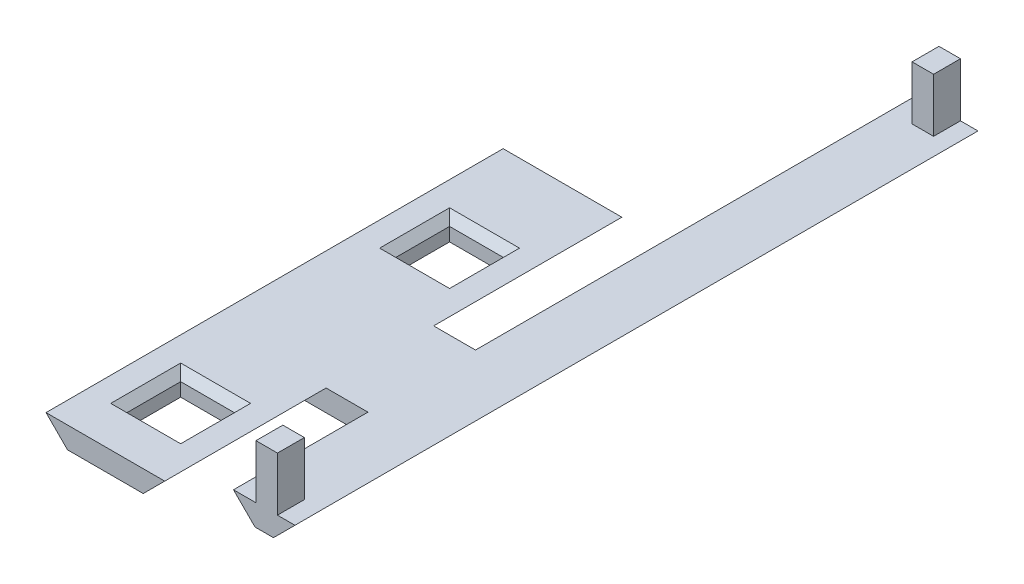
SolidWorks part; units mm, degrees
note: The reader was unsure of these and kept them because the rebuilt part matched: shared geometry of "Szkic1<4>".
ref_plane "Płaszczyzna przednia" through (0, 0, 0) normal (0, 0, 1) x (1, 0, 0)
ref_plane "Płaszczyzna górna" through (0, 0, 0) normal (0, 1, 0) x (1, 0, 0)
ref_plane "Płaszczyzna prawa" through (0, 0, 0) normal (1, 0, 0) x (0, 0, -1)
sketch "Szkic1" plane through (0, 0, 0) normal (0, 0, 1) x (1, 0, 0)
  line L0 (7.5, 0) -> (-7.5, 0)
  line L1 (-7.5, 0) -> (-11.5, 4)
  line L2 (-11.5, 4) -> (11.5, 4)
  line L3 (0, 0) -> (0, 34.0436) construction
  line L4 (7.5, 0) -> (11.5, 4)
  line L5 (-10.5787, 4) -> (-6.5787, 0)
  line L6 (10.5787, 4) -> (6.5787, 0)
  line L7 (23, 0) -> (27, 0)
  line L8 (19, 4) -> (31, 4)
  line L9 (31, 4) -> (27, 0)
  line L10 (23, 0) -> (19, 4)
  line L11 (25, 4) -> (25, 0) construction
  line L12 (19.2828, 4) -> (23.2828, 0)
  line L13 (30.7172, 4) -> (26.7172, 0)
  point P7 (0, 4)
  dimension "D1" = 45
  dimension "D2" = 15
  dimension "D3" = 4
  dimension "D4" = 0.6515
  dimension "D5" = 45
  dimension "D6" = 45
  dimension "D7" = 4
  dimension "D8" = 25
  dimension "D9" = 0.2
extrude "Dodanie-wyciągnięcie1" add sketch "Szkic1" along normal blind 85 contours L0 L3 L2 L5 | L3 L0 L6 L2
sketch "Szkic2" plane through (0, 0, 0) normal (0, -1, 0) x (1, 0, 0)
  line L0 (0.4607, 85) -> (0.4607, 0) construction
  line L1 (7.5, 85) -> (-6.5787, 85) construction
  line L3 (-4.5393, 26) -> (5.4607, 26)
  line L4 (-4.5393, 26) -> (-4.5393, 16)
  line L5 (-4.5393, 16) -> (5.4607, 16)
  line L6 (5.4607, 26) -> (5.4607, 16)
  line L7 (-4.5393, 26) -> (5.4607, 16) construction
  line L8 (-4.5393, 16) -> (5.4607, 26) construction
  line L9 (7.5, 0) -> (-6.5787, 0) construction
  line L11 (-4.5393, 76) -> (5.4607, 76)
  line L12 (-4.5393, 76) -> (-4.5393, 66)
  line L13 (-4.5393, 66) -> (5.4607, 66)
  line L14 (5.4607, 76) -> (5.4607, 66)
  line L15 (-4.5393, 76) -> (5.4607, 66) construction
  line L16 (-4.5393, 66) -> (5.4607, 76) construction
  point P4 (0.4607, 21)
  point P11 (0.4607, 71)
  dimension "D1" = 10
  dimension "D2" = 16
  dimension "D3" = 50
extrude "Wytnij-wyciągnięcie1" cut sketch "Szkic2" against normal blind 80
extrude "Dodanie-wyciągnięcie3" add sketch "Szkic1<4>" along normal blind 80 and the other way blind 47 separate body contours L13 L8 L12 L7
sketch "Szkic1<4>" plane through (0, 0, 0) normal (0, 0, 1) x (1, 0, 0) same geometry as "Szkic1"
sketch "Szkic4" plane through (0, 0, 0) normal (0, -1, 0) x (1, 0, 0)
  line L0 (7.5, 85) -> (7.5, 0) construction
  line L1 (7.5, 55) -> (23.2828, 55)
  line L2 (7.5, 55) -> (7.5, 35)
  line L3 (7.5, 35) -> (23.2828, 35)
  line L4 (23.2828, 55) -> (23.2828, 35)
  line L5 (23.2828, -47) -> (23.2828, 80) construction
  line L6 (7.5, 35) -> (7.5, 0) construction
  line L7 (7.5, 0) -> (11.5, 0) construction
  line L8 (15.3914, 35) -> (15.3914, 12) construction
  dimension "D1" = 20
  dimension "D2" = 35
  dimension "D3" = 23
extrude "Dodanie-wyciągnięcie4" add sketch "Szkic4" against normal up to vertex (4 mm away)
sketch "Szkic5" plane through (0, 4, 0) normal (0, 1, 0) x (1, 0, 0)
  line L0 (19.2828, -80) -> (30.7172, -80) construction
  line L1 (23.4607, -80) -> (27.4607, -80)
  line L2 (23.4607, -80) -> (23.4607, -75)
  line L3 (23.4607, -75) -> (27.4607, -75)
  line L4 (27.4607, -80) -> (27.4607, -75)
  line L6 (19.2828, -80) -> (30.7172, -80)
  line L7 (25.4607, -80) -> (25, -80) construction
  line M9 (19.2828, -80) -> (30.7172, -80)
  dimension "D1" = 4
  dimension "D2" = 5
  dimension "D3" = 0.4607
extrude "Dodanie-wyciągnięcie5" add sketch "Szkic5" along normal blind 10 contours L6 L4 L3 L2 M9
sketch "Szkic6" plane through (0, 4, 0) normal (0, 1, 0) x (1, 0, 0)
  line L0 (25.4607, -80) -> (25.4607, 47) construction
  line L1 (23.4607, -80) -> (27.4607, -80) construction
  line L2 (19.2828, 47) -> (30.7172, 47) construction
  line L3 (23.4607, 42) -> (23.4607, -75) construction
  line L4 (27.4607, 42) -> (23.4607, 42)
  line L5 (27.4607, 42) -> (27.4607, 47)
  line L6 (27.4607, 47) -> (23.4607, 47)
  line L7 (23.4607, 42) -> (23.4607, 47)
  line L8 (27.4607, 42) -> (23.4607, 47) construction
  line L9 (27.4607, 47) -> (23.4607, 42) construction
  point P6 (25.4607, 44.5)
  dimension "D1" = 5
extrude "Dodanie-wyciągnięcie6" add sketch "Szkic6" along normal up to vertex (10 mm away) up to point (27.4607, 14, 75)
chamfer "Sfazowanie1" distance 1.5 angle 45 8 edges at (5.4607, 4, 21) (0.4607, 4, 16) (-4.5393, 4, 21) (0.4607, 4, 26) (0.4607, 4, 66) (5.4607, 4, 71) (0.4607, 4, 76) (-4.5393, 4, 71)
